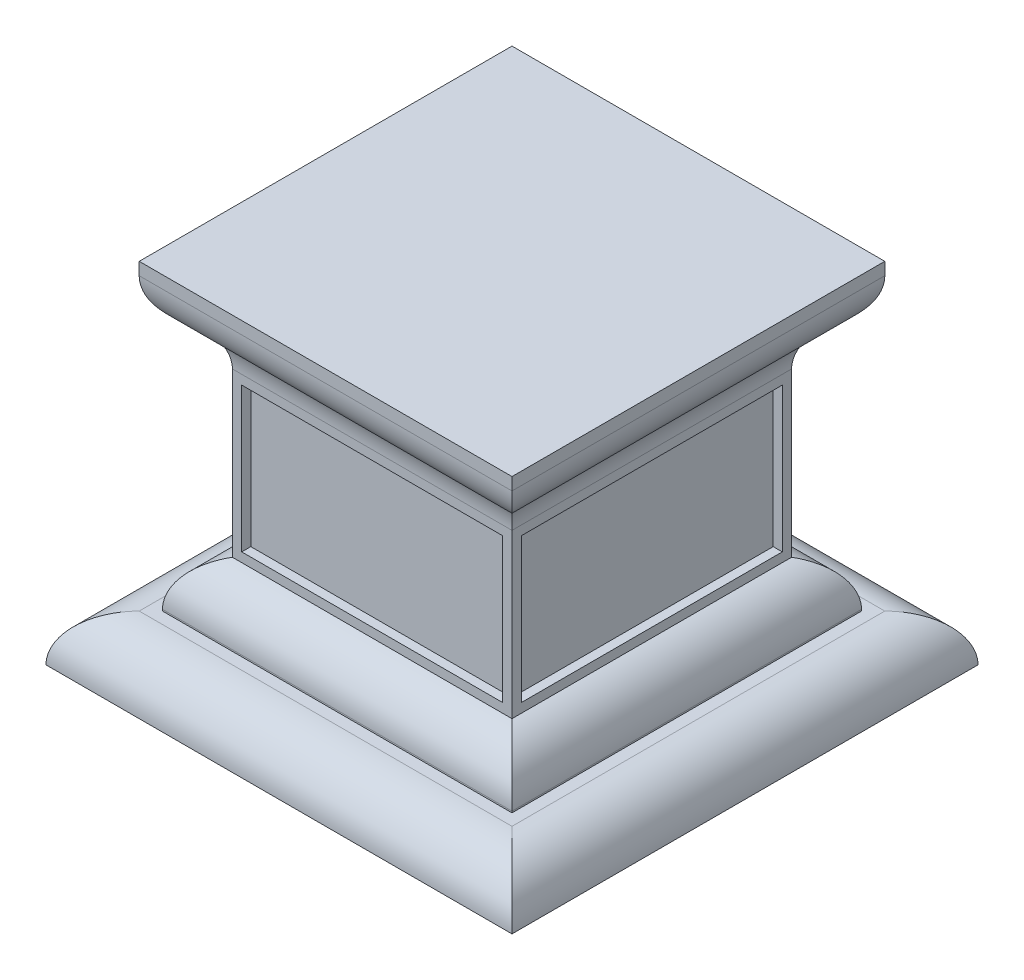
SolidWorks part; units mm, degrees
ref_plane "Front Plane" through (0, 0, 0) normal (0, 0, 1) x (1, 0, 0)
ref_plane "Top Plane" through (0, 0, 0) normal (0, 1, 0) x (1, 0, 0)
ref_plane "Right Plane" through (0, 0, 0) normal (1, 0, 0) x (0, 0, -1)
sketch "Sketch1" plane through (0, 0, 0) normal (0, 0, 1) x (1, 0, 0)
  line L0 (-50, 0) -> (50, 0)
  line L1 (50, 0) -> (50, 10)
  line L2 (50, 10) -> (37.5, 10)
  line L3 (37.5, 10) -> (37.5, 20)
  line L4 (37.5, 20) -> (30, 20)
  line L5 (30, 20) -> (30, 65)
  line L6 (30, 65) -> (40, 65)
  line L7 (40, 65) -> (40, 75)
  line L8 (40, 75) -> (-40, 75)
  line L9 (-40, 75) -> (-40, 65)
  line L10 (-40, 65) -> (-30, 65)
  line L11 (-30, 65) -> (-30, 20)
  line L12 (-30, 20) -> (-37.5, 20)
  line L13 (-37.5, 20) -> (-37.5, 10)
  line L14 (-37.5, 10) -> (-50, 10)
  line L15 (-50, 10) -> (-50, 0)
  line L16 (-37.5, 10) -> (37.5, 10) construction
  line L17 (30, 20) -> (-30, 20) construction
  line L18 (-30, 65) -> (30, 65) construction
  point P3 (0, 0)
  point P14 (0, 10)
  point P18 (0, 20)
  point P20 (0, 65)
  point P21 (37.5, 15)
  point P22 (0, 75)
  point P23 (0, 0)
  point P24 (0, 0)
  point P25 (0, 0)
  point P26 (0, 0)
  dimension "D1" = 100
  dimension "D2" = 75
  dimension "D3" = 60
  dimension "D4" = 10
  dimension "D5" = 10
  dimension "D6" = 45
  dimension "D7" = 10
  dimension "D8" = 80
sketch "Sketch2" plane through (0, 0, 0) normal (0, 1, 0) x (1, 0, 0)
  line L0 (-37.5, 0) -> (37.5, 0) construction
  line L1 (-50, 50) -> (50, 50)
  line L2 (-50, 50) -> (-50, -50)
  line L3 (-50, -50) -> (50, -50)
  line L4 (50, 50) -> (50, -50)
  line L5 (-50, 50) -> (50, -50) construction
  line L6 (-50, -50) -> (50, 50) construction
  line L7 (-50, 0) -> (50, 0) construction
  point P0 (0, 0)
extrude "Boss-Extrude1" add sketch "Sketch2" along normal blind 10
sketch "Sketch3" plane through (0, 10, 0) normal (0, 1, 0) x (1, 0, 0)
  line L1 (-37.5, 37.5) -> (37.5, 37.5)
  line L2 (-37.5, 37.5) -> (-37.5, -37.5)
  line L3 (-37.5, -37.5) -> (37.5, -37.5)
  line L4 (37.5, 37.5) -> (37.5, -37.5)
  line L5 (-37.5, 37.5) -> (37.5, -37.5) construction
  line L6 (-37.5, -37.5) -> (37.5, 37.5) construction
extrude "Boss-Extrude2" add sketch "Sketch3" along normal blind 10
sketch "Sketch4" plane through (0, 20, 0) normal (0, 1, 0) x (1, 0, 0)
  line L1 (-30, 30) -> (30, 30)
  line L2 (-30, 30) -> (-30, -30)
  line L3 (-30, -30) -> (30, -30)
  line L4 (30, 30) -> (30, -30)
  line L5 (-30, 30) -> (30, -30) construction
  line L6 (-30, -30) -> (30, 30) construction
  point P0 (0, 0)
extrude "Boss-Extrude3" add sketch "Sketch4" along normal blind 45
sketch "Sketch5" plane through (0, 65, 0) normal (0, 1, 0) x (1, 0, 0)
  line L1 (-40, 40) -> (40, 40)
  line L2 (-40, 40) -> (-40, -40)
  line L3 (-40, -40) -> (40, -40)
  line L4 (40, 40) -> (40, -40)
  line L5 (-40, 40) -> (40, -40) construction
  line L6 (-40, -40) -> (40, 40) construction
  point P0 (0, 0)
extrude "Boss-Extrude4" add sketch "Sketch5" along normal blind 10
fillet "Fillet2" radius 10 8 edges at (-50, 10, 0) (0, 10, 50) (0, 10, -50) (50, 10, 0) (-37.5, 20, 0) (0, 20, -37.5) (37.5, 20, 0) (0, 20, 37.5)
fillet "Fillet1" radius 10 4 edges at (30, 65, 0) (0, 65, 30) (-30, 65, 0) (0, 65, -30)
fillet "Fillet3" radius 10 4 edges at (0, 65, 40) (-40, 65, 0) (0, 65, -40) (40, 65, 0)
sketch "Sketch6" plane through (0, 0, 30) normal (0, 0, 1) x (1, 0, 0)
  line L0 (-30, 55) -> (-30, 20) construction
  line L1 (-28, 53) -> (28, 53)
  line L2 (-28, 53) -> (-28, 22)
  line L3 (-28, 22) -> (28, 22)
  line L4 (28, 53) -> (28, 22)
  line L5 (30, 55) -> (30, 20) construction
  line L6 (-30, 20) -> (30, 20) construction
  line L7 (30, 55) -> (-30, 55) construction
  dimension "D1" = 2
  dimension "D2" = 2
  dimension "D3" = 2
  dimension "D4" = 2
extrude "Cut-Extrude1" cut sketch "Sketch6" against normal blind 1.95
ref_axis "Axis2" through (0, 78.75, 0) along (0, -1, 0)
pattern_circular "CirPattern2" count 4 over 360 about axis through (0, 78.75, 0) along (0, -1, 0) of "Cut-Extrude1"
